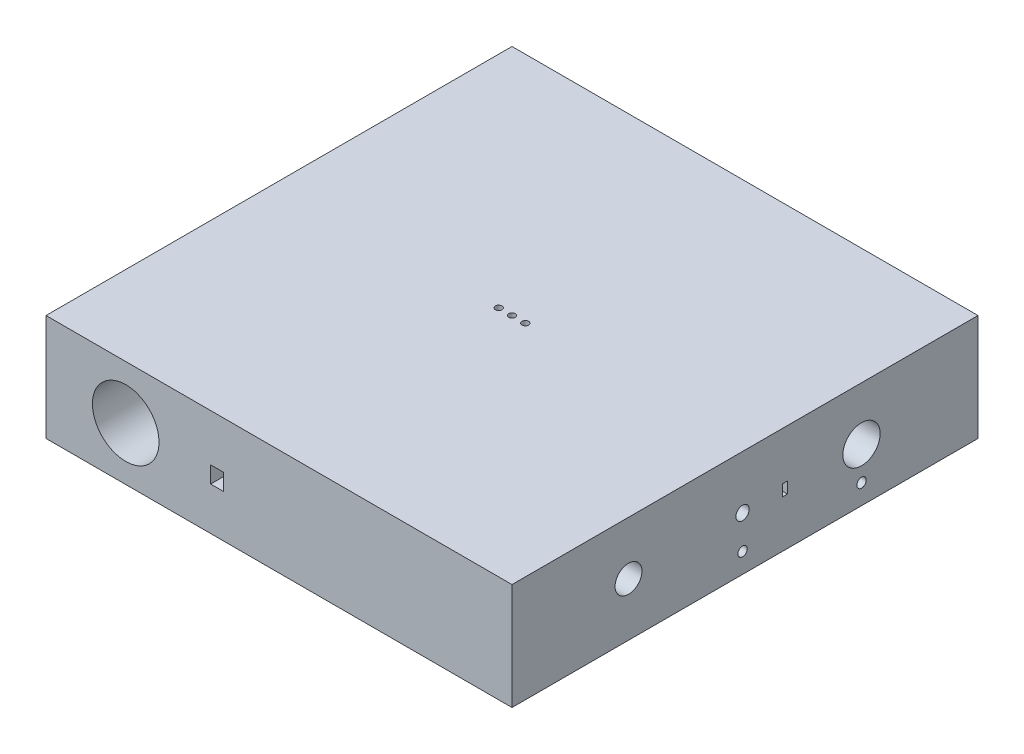
SolidWorks part; units mm, degrees
ref_plane "Front Plane" through (0, 0, 0) normal (0, 0, 1) x (1, 0, 0)
ref_plane "Top Plane" through (0, 0, 0) normal (0, 1, 0) x (1, 0, 0)
ref_plane "Right Plane" through (0, 0, 0) normal (1, 0, 0) x (0, 0, -1)
sketch "Sketch1" plane through (0, 0, 0) normal (0, 1, 0) x (1, 0, 0)
  line L1 (-175, 175) -> (175, 175)
  line L2 (-175, 175) -> (-175, -175)
  line L3 (-175, -175) -> (175, -175)
  line L4 (175, 175) -> (175, -175)
  line L5 (-175, 175) -> (175, -175) construction
  line L6 (-175, -175) -> (175, 175) construction
  point P0 (0, 0)
  dimension "D1" = 350
  dimension "D2" = 350
extrude "Boss-Extrude1" add sketch "Sketch1" along normal blind 80
sketch "Sketch2" plane through (0, 80, 0) normal (0, 1, 0) x (1, 0, 0)
  line L0 (0, 0) -> (0, 175)
  line L1 (175, 175) -> (-175, 175) construction
  line L2 (175, -175) -> (175, 175) construction
  circle A0 centre (0, 0) radius 2.5
  circle A1 centre (10, 0) radius 2.5
  circle A2 centre (-10, 0) radius 2.5
  point P7 (175, 0)
  dimension "D1" = 5
  dimension "D5" = 5
  dimension "D6" = 5
  dimension "D2" = 175
  dimension "D3" = 175
  dimension "D4" = 10
  dimension "D7" = 10
  dimension "D8" = 175
  dimension "D9" = 175
extrude "Cut-Extrude1" cut sketch "Sketch2" against normal through all contours A0 region at (-1.7178, 80, 1.7178)
extrude "Cut-Extrude2" cut sketch "Sketch2<4>" against normal through all contours A1 region at (10, 80, 0)
sketch "Sketch2<4>" plane through (0, 80, 0) normal (0, 1, 0) x (1, 0, 0) same geometry as "Sketch2"
extrude "Cut-Extrude3" cut sketch "Sketch2<5>" against normal through all contours A2 region at (-10, 80, 0)
sketch "Sketch2<5>" plane through (0, 80, 0) normal (0, 1, 0) x (1, 0, 0) same geometry as "Sketch2"
sketch "Sketch3" plane through (-175, 0, 0) normal (-1, 0, 0) x (0, 0, 1)
  line L0 (-175, 80) -> (-175, 0) construction
  line L1 (-28.15, 35.4316) -> (-31.85, 35.4316)
  line L2 (-28.15, 35.4316) -> (-28.15, 43.9316)
  line L3 (-28.15, 43.9316) -> (-31.85, 43.9316)
  line L4 (-31.85, 35.4316) -> (-31.85, 43.9316)
  line L5 (-28.15, 35.4316) -> (-31.85, 43.9316) construction
  line L6 (-28.15, 43.9316) -> (-31.85, 35.4316) construction
  point P0 (-30, 39.6816)
  point P7 (-175, 40)
  dimension "D1" = 8.5
  dimension "D2" = 3.7
  dimension "D3" = 145
extrude "Cut-Extrude4" cut sketch "Sketch3" against normal through all
sketch "Sketch4" plane through (-175, 0, 0) normal (-1, 0, 0) x (0, 0, 1)
  line L0 (175, 80) -> (175, 0) construction
  line L3 (-175, 0) -> (175, 0) construction
  circle A0 centre (87.5, 40) radius 10.1
  point P6 (86.9487, 0)
  point P7 (86.3694, 0)
  dimension "D1" = 20.2
  dimension "D2" = 87.5
  dimension "D3" = 40
extrude "Cut-Extrude5" cut sketch "Sketch4" against normal through all
sketch "Sketch6" plane through (-175, 0, 0) normal (-1, 0, 0) x (0, 0, 1)
  line L0 (-28.15, 35.4316) -> (-28.15, 43.9316) construction
  line L1 (-175, 0) -> (175, 0) construction
  circle A0 centre (1.85, 15) radius 3.555
  point P2 (32.6777, 25.3503)
  point P5 (-28.15, 39.6816)
  dimension "D1" = 7.11
  dimension "D2" = 30
  dimension "D3" = 15
extrude "Cut-Extrude7" cut sketch "Sketch6" against normal through all and the other way blind 10
sketch "Sketch7" plane through (-175, 0, 0) normal (-1, 0, 0) x (0, 0, 1)
  line L0 (-175, 80) -> (-175, 0) construction
  line L1 (-175, 0) -> (175, 0) construction
  circle A0 centre (-87.5, 15) radius 3.555
  dimension "D1" = 7.11
  dimension "D2" = 87.5
  dimension "D3" = 15
extrude "Cut-Extrude8" cut sketch "Sketch7" against normal through all
sketch "Sketch9" plane through (-175, 0, 0) normal (-1, 0, 0) x (0, 0, 1)
  line L0 (-175, 80) -> (-175, 0) construction
  line L1 (-175, 0) -> (175, 0) construction
  circle A0 centre (-87.5, 40) radius 14
  dimension "D1" = 28
  dimension "D2" = 87.5
  dimension "D3" = 40
extrude "Cut-Extrude10" cut sketch "Sketch9" against normal through all
sketch "Sketch11" plane through (-175, 0, 0) normal (-1, 0, 0) x (0, 0, 1)
  line L3 (-28.15, 35.4316) -> (-28.15, 43.9316) construction
  line L4 (-175, 0) -> (175, 0) construction
  circle A0 centre (1.85, 40) radius 5.025
  point P4 (15.9829, 40.0588)
  point P6 (-4.6138, 39.3197)
  dimension "D1" = 10.05
  dimension "D2" = 30
  dimension "D3" = 40
extrude "Cut-Extrude12" cut sketch "Sketch11" against normal through all
sketch "Sketch13" plane through (0, 0, -175) normal (0, 0, -1) x (-1, 0, 0)
  line L0 (-175, 0) -> (175, 0) construction
  circle A0 centre (115.112, 40) radius 25
  dimension "D1" = 50
  dimension "D2" = 40
extrude "Cut-Extrude14" cut sketch "Sketch13" against normal through all
sketch "Sketch14" plane through (0, 0, -175) normal (0, 0, -1) x (-1, 0, 0)
  line L1 (51.3298, 32.1941) -> (41.6298, 32.1941)
  line L2 (51.3298, 32.1941) -> (51.3298, 44.6941)
  line L3 (51.3298, 44.6941) -> (41.6298, 44.6941)
  line L4 (41.6298, 32.1941) -> (41.6298, 44.6941)
  line L5 (51.3298, 32.1941) -> (41.6298, 44.6941) construction
  line L6 (51.3298, 44.6941) -> (41.6298, 32.1941) construction
  point P0 (46.4798, 38.4441)
  dimension "D1" = 9.7
  dimension "D2" = 12.5
extrude "Cut-Extrude18" cut sketch "Sketch14" against normal through all
